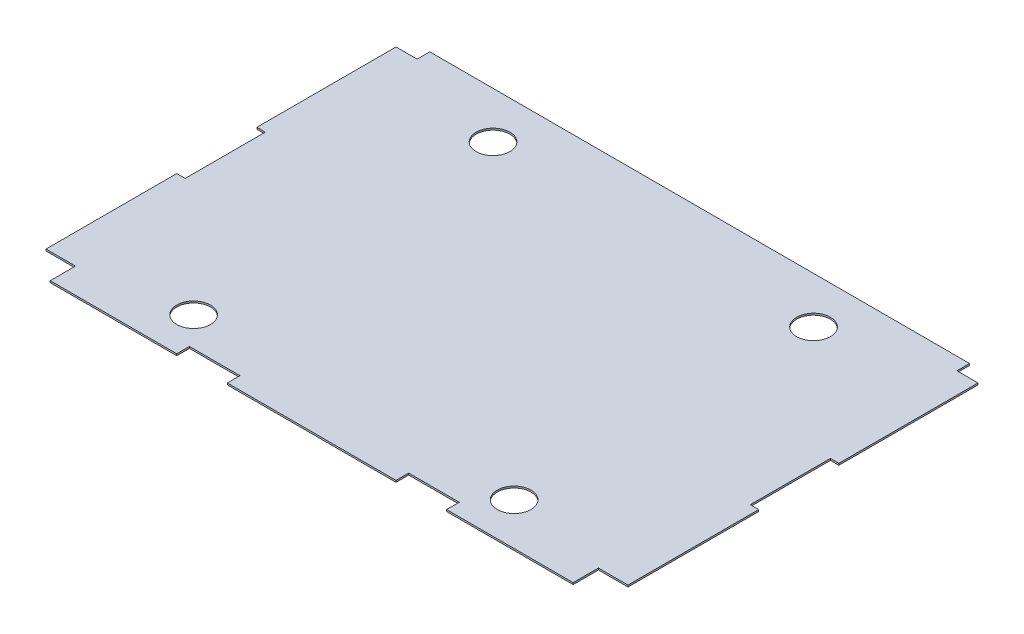
SolidWorks part; units mm, degrees
ref_plane "Front Plane" through (0, 0, 0) normal (0, 0, 1) x (1, 0, 0)
ref_plane "Top Plane" through (0, 0, 0) normal (0, 1, 0) x (1, 0, 0)
ref_plane "Right Plane" through (0, 0, 0) normal (1, 0, 0) x (0, 0, -1)
sketch "Sketch1" plane through (0, 0, 0) normal (0, 1, 0) x (1, 0, 0)
  line L0 (-457.2, -292.1) -> (457.2, -292.1) construction
  line L1 (457.2, 304.8) -> (-457.2, 304.8) construction
  line L2 (457.2, 304.8) -> (457.2, -304.8) construction
  line L3 (457.2, -304.8) -> (-457.2, -304.8) construction
  line L4 (-457.2, 304.8) -> (-457.2, -304.8) construction
  line L5 (457.2, 304.8) -> (-457.2, -304.8) construction
  line L6 (457.2, -304.8) -> (-457.2, 304.8) construction
  line L7 (438.15, -304.8) -> (438.15, 304.8) construction
  line L8 (-438.15, 273.05) -> (-406.4, 273.05)
  line L9 (-406.4, 273.05) -> (-406.4, 292.1)
  line L10 (-406.4, 292.1) -> (406.4, 292.1)
  line L11 (406.4, 292.1) -> (406.4, 273.05)
  line L12 (406.4, 273.05) -> (438.15, 273.05)
  line L13 (-438.15, -304.8) -> (-438.15, 304.8) construction
  line L14 (-457.2, 292.1) -> (457.2, 292.1) construction
  line L15 (438.15, 273.05) -> (438.15, 63.5)
  line L16 (438.15, 63.5) -> (425.45, 63.5)
  line L17 (425.45, 63.5) -> (425.45, -57.15)
  line L18 (425.45, -57.15) -> (438.15, -57.15)
  line L19 (438.15, -57.15) -> (438.15, -254)
  line L20 (438.15, -254) -> (393.7, -254)
  line L21 (393.7, -254) -> (393.7, -292.1)
  line L22 (393.7, -292.1) -> (203.2, -292.1)
  line L23 (203.2, -292.1) -> (203.2, -273.05)
  line L24 (203.2, -273.05) -> (127, -273.05)
  line L25 (127, -273.05) -> (127, -292.1)
  line L26 (127, -292.1) -> (-127, -292.1)
  line L27 (-127, -292.1) -> (-127, -273.05)
  line L28 (-127, -273.05) -> (-203.2, -273.05)
  line L29 (-203.2, -273.05) -> (-203.2, -292.1)
  line L30 (-203.2, -292.1) -> (-393.7, -292.1)
  line L31 (-393.7, -292.1) -> (-393.7, -254)
  line L32 (-393.7, -254) -> (-438.15, -254)
  line L33 (-438.15, -254) -> (-438.15, -57.15)
  line L34 (-438.15, -57.15) -> (-425.45, -57.15)
  line L35 (-425.45, -57.15) -> (-425.45, 63.5)
  line L36 (-425.45, 63.5) -> (-438.15, 63.5)
  line L37 (-438.15, 63.5) -> (-438.15, 273.05)
  line L38 (0, 304.8) -> (0, -304.8) construction
  circle A0 centre (241.3, 222.25) radius 25.4
  circle A1 centre (241.3, -228.6) radius 25.4
  circle A2 centre (-241.3, 222.25) radius 25.4
  circle A3 centre (-241.3, -228.6) radius 25.4
  point P0 (0, 0)
  dimension "D35" = 50.8
  dimension "D36" = 50.8
  dimension "D1" = 914.4
  dimension "D2" = 609.6
  dimension "D3" = 12.7
  dimension "D4" = 19.05
  dimension "D5" = 31.75
  dimension "D6" = 50.8
  dimension "D7" = 31.75
  dimension "D8" = 19.05
  dimension "D9" = 12.7
  dimension "D10" = 50.8
  dimension "D11" = 241.3
  dimension "D12" = 31.75
  dimension "D13" = 31.75
  dimension "D14" = 361.95
  dimension "D15" = 558.8
  dimension "D16" = 63.5
  dimension "D17" = 254
  dimension "D18" = 31.75
  dimension "D19" = 31.75
  dimension "D20" = 330.2
  dimension "D21" = 584.2
  dimension "D22" = 660.4
  dimension "D23" = 850.9
  dimension "D24" = 190.5
  dimension "D25" = 76.2
  dimension "D26" = 254
  dimension "D27" = 76.2
  dimension "D28" = 190.5
  dimension "D29" = 38.1
  dimension "D30" = 558.8
  dimension "D31" = 241.3
  dimension "D32" = 361.95
  dimension "D33" = 215.9
  dimension "D34" = 82.55
  dimension "D37" = 533.4
  dimension "D38" = 215.9
extrude "Boss-Extrude1" add sketch "Sketch1" along normal blind 2.6568
